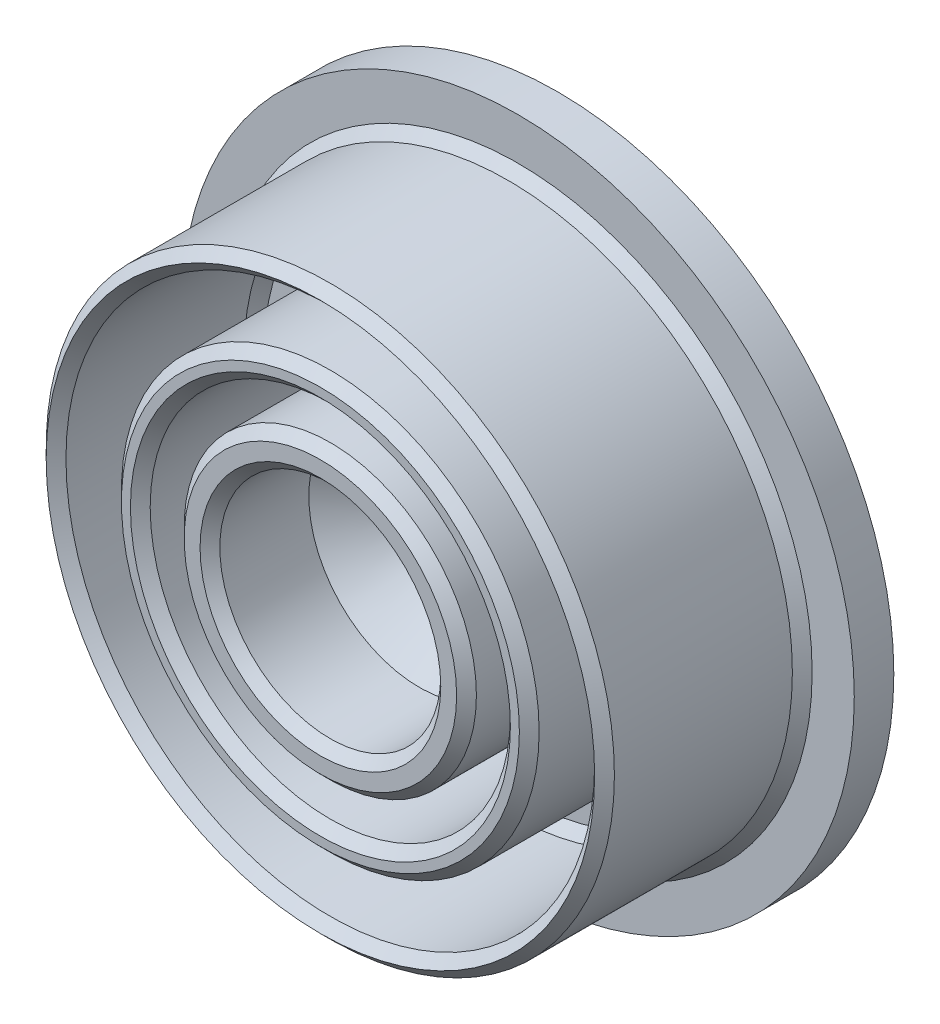
SolidWorks part; units mm, degrees
material "moto_Chrome Stainless Steel"
ref_plane "Front Plane" through (0, 0, 0) normal (0, 0, 1) x (1, 0, 0)
ref_plane "Top Plane" through (0, 0, 0) normal (0, 1, 0) x (1, 0, 0)
ref_plane "Right Plane" through (0, 0, 0) normal (1, 0, 0) x (0, 0, -1)
sketch "Sketch1" plane through (0, 0, 0) normal (0, 0, 1) x (1, 0, 0)
  circle A0 centre (0, 0) radius 17
  circle A1 centre (0, 0) radius 15.7962
  circle A2 centre (0, 0) radius 10.5623
  circle A3 centre (0, 0) radius 9.1086
  circle A4 centre (0, 0) radius 13.3691
  circle A5 centre (0, 0) radius 14.3691
  circle A6 centre (0, 0) radius 7.39
  circle A7 centre (0, 0) radius 5.5872
  dimension "D1" = 34
  dimension "D2" = 1
extrude "Boss-Extrude1" add sketch "Sketch1" against normal blind 2 contours A0 A1 | A1 A5 | A5 A4 | A4 A2 | A2 A3 | A3 A6 | A6 A7 | A7 region at (-16.5192, 0, 0) region at (-15.3494, 0, 0) region at (-10.2636, 0, 0) region at (-8.851, 0, 0) region at (-12.991, 0, 0) region at (-13.9627, 0, 0) region at (-7.181, 0, 0) region at (0, 0, 0)
extrude "Boss-Extrude2" add sketch "Sketch1<3>" along normal blind 10 contours A5 A4 | A2 A3 | A6 A7 region at (-10.2636, 0, 0) region at (-13.9627, 0, 0) region at (-7.181, 0, 0)
sketch "Sketch1<3>" plane through (0, 0, 0) normal (0, 0, 1) x (1, 0, 0) same geometry as "Sketch1"
chamfer "Chamfer3" distance 5 angle 45 1 edges at (5.5872, 0, 0)
chamfer "Chamfer4" distance 0.5 angle 45 5 edges at (9.1086, 0, 0) (7.39, 0, 0) (10.5623, 0, 0) (13.3691, 0, 0) (14.3691, 0, 0)
chamfer "Chamfer5" distance 0.5 angle 45 6 edges at (5.5872, 0, 10) (7.39, 0, 10) (9.1086, 0, 10) (10.5623, 0, 10) (13.3691, 0, 10) (14.3691, 0, 10)
